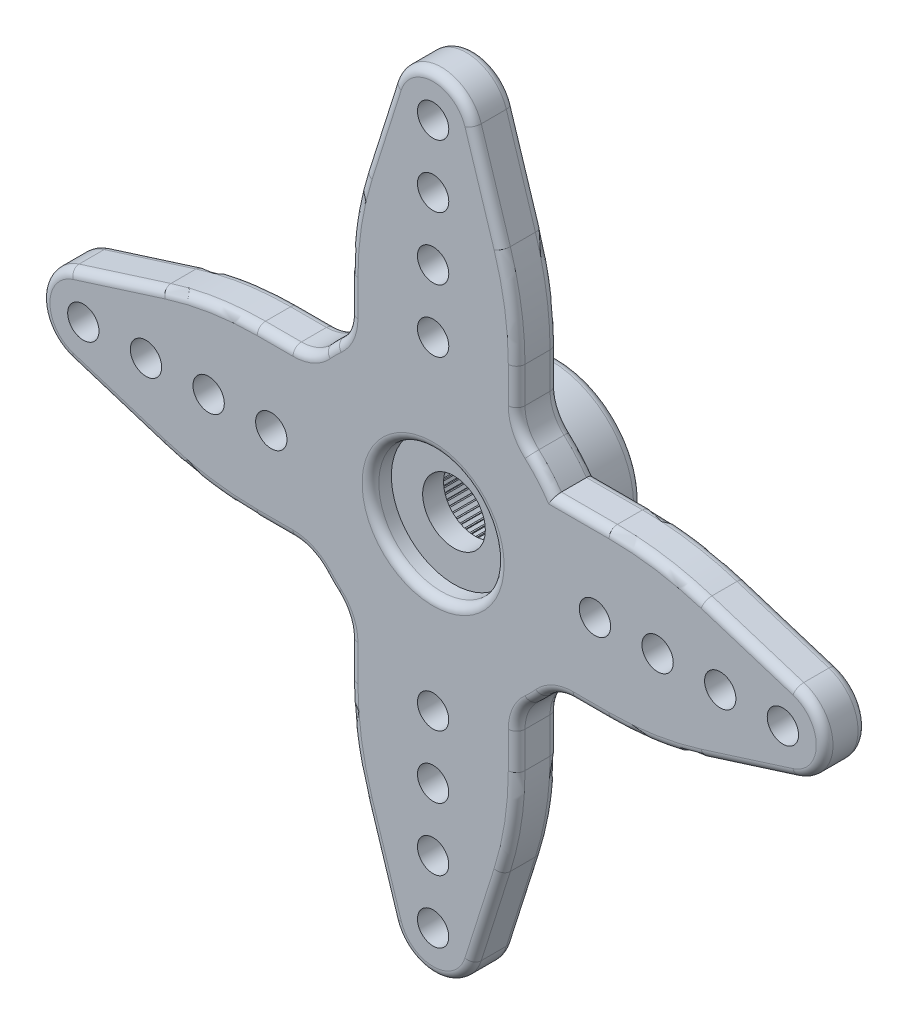
SolidWorks part; units mm, degrees
ref_plane "Ön Düzlem" through (0, 0, 0) normal (0, 0, 1) x (1, 0, 0)
ref_plane "Üst Düzlem" through (0, 0, 0) normal (0, 1, 0) x (1, 0, 0)
ref_plane "Sağ Düzlem" through (0, 0, 0) normal (1, 0, 0) x (0, 0, -1)
sketch "Sketch1" plane through (0, 0, 0) normal (0, 0, 1) x (1, 0, 0)
  line L0 (-4, 10.7446) -> (-4, 5.7446)
  line L1 (4, 10.7446) -> (4, 5.7446)
  line L2 (0, 0) -> (0, 16.75) construction
  line L3 (-4, 5.7446) -> (4, 5.7446) construction
  line L4 (-1.9067, 17.3539) -> (-4, 10.7446)
  line L5 (1.9067, 17.3539) -> (4, 10.7446)
  circle A0 centre (0, 0) radius 7
  circle A1 centre (0, 0) radius 18.75
  circle A2 centre (0, 16.75) radius 2
  circle A3 centre (0, 0) radius 1.5
  dimension "D1" = 37.5
  dimension "D2" = 14
  dimension "D3" = 4
  dimension "D5" = 3
  dimension "D4" = 5
  dimension "D6" = 8
extrude "Boss-Extrude1" add sketch "Sketch1" along normal blind 2 contours A0 A3 | A2 L4 L0 A0 L1 L5 | A2 region at (0, 10.6981, 0) region at (0, 6.802, 0) region at (0, 16.75, 0)
fillet "Fillet1" radius 15 2 edges at (-4, 10.7446, 1) (4, 10.7446, 1)
sketch "Sketch2" plane through (0, 0, 2) normal (0, 0, 1) x (1, 0, 0)
  line L0 (0, 0) -> (0, 18.75) construction
  arc A0 (1.9067, 17.3539) -> (-1.9067, 17.3539) centre (0, 16.75) ccw construction
  circle A1 centre (0, 16.75) radius 0.75
  circle A2 centre (0, 13.75) radius 0.75
  circle A3 centre (0, 10.75) radius 0.75
  circle A4 centre (0, 7.75) radius 0.75
  dimension "D1" = 1.5
  dimension "D2" = 2
  dimension "D3" = 4
extrude "Cut-Extrude1" cut sketch "Sketch2" against normal through all
pattern_circular "CirPattern2" count 4 over 360 about axis through (0, 0, 2) along (0, 0, 1) of "Boss-Extrude1", "Fillet1", "Cut-Extrude1"
fillet "Fillet2" radius 2 7 edges at (4, 5.7446, 1) (-4, 5.7446, 1) (5.7446, -4, 1) (4, -5.7446, 1) (-5.7446, 4, 1) (-4, -5.7446, 1) (-5.7446, -4, 1)
sketch "Sketch3" plane through (0, 0, 2) normal (0, 0, 1) x (1, 0, 0)
  circle A0 centre (0, 0) radius 3
  dimension "D1" = 6
extrude "Cut-Extrude2" cut sketch "Sketch3" against normal blind 1
sketch "Sketch4" plane through (0, 0, 0) normal (0, 0, -1) x (-1, 0, 0)
  circle A0 centre (0, 0) radius 4
  circle A1 centre (0, 0) radius 3
  dimension "D1" = 8
  dimension "D2" = 6
extrude "Boss-Extrude2" add sketch "Sketch4" along normal blind 4
sketch "Sketch5" plane through (0, 0, -4) normal (0, 0, -1) x (-1, 0, 0)
  line L0 (0, 0) -> (0, -4) construction
  line L2 (0.025, -2.8941) -> (-0.025, -2.8941)
  line L3 (0.025, -2.8941) -> (0.025, -3.3941)
  line L4 (0.025, -3.3941) -> (-0.025, -3.3941)
  line L5 (-0.025, -2.8941) -> (-0.025, -3.3941)
  line L6 (0.025, -2.8941) -> (-0.025, -3.3941) construction
  line L7 (0.025, -3.3941) -> (-0.025, -2.8941) construction
  circle A1 centre (0, 0) radius 4 construction
  point P0 (0, -3.1441)
  dimension "D1" = 0.05
  dimension "D2" = 0.5
extrude "Boss-Extrude3" add sketch "Sketch5" against normal up to surface (4 mm away) up to face at (7.75, -0.75, 0)
pattern_circular "CirPattern3" count 80 over 360 about axis through (0, 0, -4) along (0, 0, -1) of "Boss-Extrude3"
fillet "Fillet3" radius 0.4 81 edges at (7.0852, 4, 0) (10.7173, 3.8239, 0) (15.1545, 2.6033, 0) (18.75, 0, 0) (15.1545, -2.6033, 0) (10.7173, -3.8239, 0) (7.567, -4, 0) (5.8917, -4.1743, 0) (4.9497, -4.9497, 0) (4.1743, -5.8917, 0) (4, -7.567, 0) (3.8239, -10.7173, 0) (2.6033, -15.1545, 0) (0, -18.75, 0) (-2.6033, -15.1545, 0) (-3.8239, -10.7173, 0) (-4, -7.567, 0) (-4.1743, -5.8917, 0) (-4.9497, -4.9497, 0) (-5.8917, -4.1743, 0) (-7.567, -4, 0) (-10.7173, -3.8239, 0) (-15.1545, -2.6033, 0) (-18.75, 0, 0) (-15.1545, 2.6033, 0) (-10.7173, 3.8239, 0) (-7.567, 4, 0) (-5.8917, 4.1743, 0) (-4.9497, 4.9497, 0) (-4.1743, 5.8917, 0) (-4, 7.567, 0) (-3.8239, 10.7173, 0) (-2.6033, 15.1545, 0) (0, 18.75, 0) (5.2411, 4.6402, 0) (4.1743, 5.8917, 0) (4, 7.567, 0) (3.8239, 10.7173, 0) (7.0852, 4, 2) (10.7173, 3.8239, 2) (15.1545, 2.6033, 2) (18.75, 0, 2) (15.1545, -2.6033, 2) (10.7173, -3.8239, 2) (7.567, -4, 2) (5.8917, -4.1743, 2) (4.9497, -4.9497, 2) (4.1743, -5.8917, 2) (4, -7.567, 2) (3.8239, -10.7173, 2) (2.6033, -15.1545, 2) (0, -18.75, 2) (-2.6033, -15.1545, 2) (-3.8239, -10.7173, 2) (-4, -7.567, 2) (-4.1743, -5.8917, 2) (-4.9497, -4.9497, 2) (-5.8917, -4.1743, 2) (-7.567, -4, 2) (-10.7173, -3.8239, 2) (-15.1545, -2.6033, 2) (-18.75, 0, 2) (-15.1545, 2.6033, 2) (-10.7173, 3.8239, 2) (-7.567, 4, 2) (-5.8917, 4.1743, 2) (-4.9497, 4.9497, 2) (-4.1743, 5.8917, 2) (-4, 7.567, 2) (-3.8239, 10.7173, 2) (-2.6033, 15.1545, 2) (0, 18.75, 2) (5.2411, 4.6402, 2) (4.1743, 5.8917, 2) (4, 7.567, 2) (3.8239, 10.7173, 2) (2.6033, 15.1545, 0) (2.6033, 15.1545, 2) (3, 0, 2) (-4, 0, -4) (4, 0, 0)
